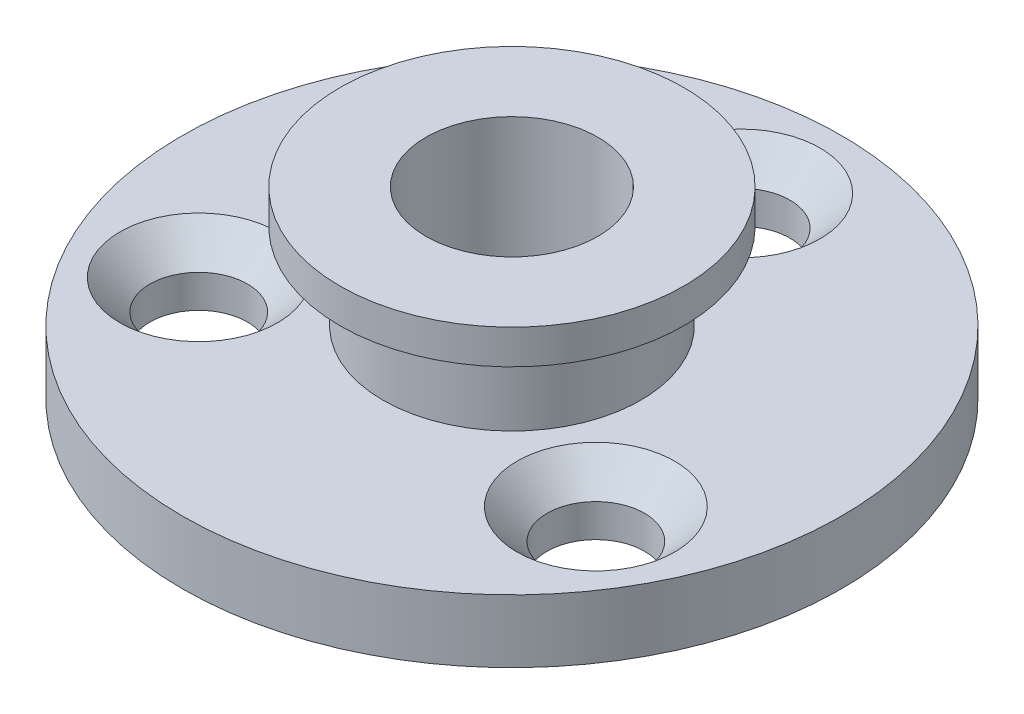
SolidWorks part; units mm, degrees
ref_plane "Plan de face" through (0, 0, 0) normal (0, 0, 1) x (1, 0, 0)
ref_plane "Plan de dessus" through (0, 0, 0) normal (0, 1, 0) x (1, 0, 0)
ref_plane "Plan de droite" through (0, 0, 0) normal (1, 0, 0) x (0, 0, -1)
sketch "Esquisse1" plane through (0, 0, 0) normal (0, 0, 1) x (1, 0, 0)
  line L0 (0, 4.6899) -> (0, -3.9873) construction
  line L1 (3, -3.2) -> (3, 3.2)
  line L2 (3, 3.2) -> (6, 3.2)
  line L3 (6, 3.2) -> (6, 2)
  line L4 (6, 2) -> (4.5, 2)
  line L5 (4.5, 2) -> (4.5, -1)
  line L6 (4.5, -1) -> (11.5, -1)
  line L7 (11.5, -1) -> (11.5, -3.2)
  line L8 (11.5, -3.2) -> (3, -3.2)
  point P5 (4.5, 0.5)
  point P12 (3, 0)
  dimension "D1" = 1.2
  dimension "D2" = 2.2
  dimension "D3" = 3
  dimension "D4" = 3
  dimension "D5" = 1.5
  dimension "D6" = 1.5
  dimension "D7" = 11.5
revolve "Révolution1" add sketch "Esquisse1" angle 360 about L0
sketch "Esquisse2" plane through (0, -1, 0) normal (0, 1, 0) x (1, 0, 0)
  line L0 (0, 0) -> (0, 8) construction
  line L1 (0, 0) -> (6.9282, -4) construction
  line L2 (0, 0) -> (-6.9282, -4) construction
  circle A0 centre (0, 0) radius 8 construction
  circle A1 centre (0, 8) radius 1.7 construction
  circle A2 centre (0, 8) radius 2.85 construction
  circle A3 centre (6.9282, -4) radius 2.85 construction
  circle A4 centre (6.9282, -4) radius 1.7 construction
  circle A5 centre (-6.9282, -4) radius 2.85 construction
  circle A6 centre (-6.9282, -4) radius 1.7 construction
  point P14 (0, 0)
  dimension "D1" = 16
  dimension "D2" = 3.4
  dimension "D3" = 5.7
  dimension "D4" = 3
hole_wizard "CSK for M3 Flat Head Machine Screw1" positions "Esquisse5" profile "Esquisse4" countersink size "M3" standard "ANSI Metric" end condition through all
sketch "Esquisse5" plane through (0, -1, 0) normal (0, 1, 0) x (1, 0, 0)
  point P0 (-6.9282, -4)
  point P3 (6.9282, -4)
  point P6 (0, 8)
sketch "Esquisse4" plane through (-6.9282, -1, 4) normal (1, 0, 0) x (0, 0, 1)
  line L0 (0, 0) -> (0, 2.2)
  line L1 (0, 2.2) -> (1.7, 2.2)
  line L2 (1.7, 2.2) -> (1.7, 1.05)
  line L3 (1.7, 1.05) -> (2.75, 0)
  line L5 (2.75, 0) -> (0, 0)
  line L6 (-1.7, 1.05) -> (-2.75, 0) construction
  line L11 (0, -6.35) -> (0, 107.95) construction
  dimension "Thru Hole Dia." = 3.4
  dimension "Thru Hole Depth" = 2.2
  dimension "Near C'Sink Dia." = 5.5
  dimension "Near C'Sink Angle" = 90
